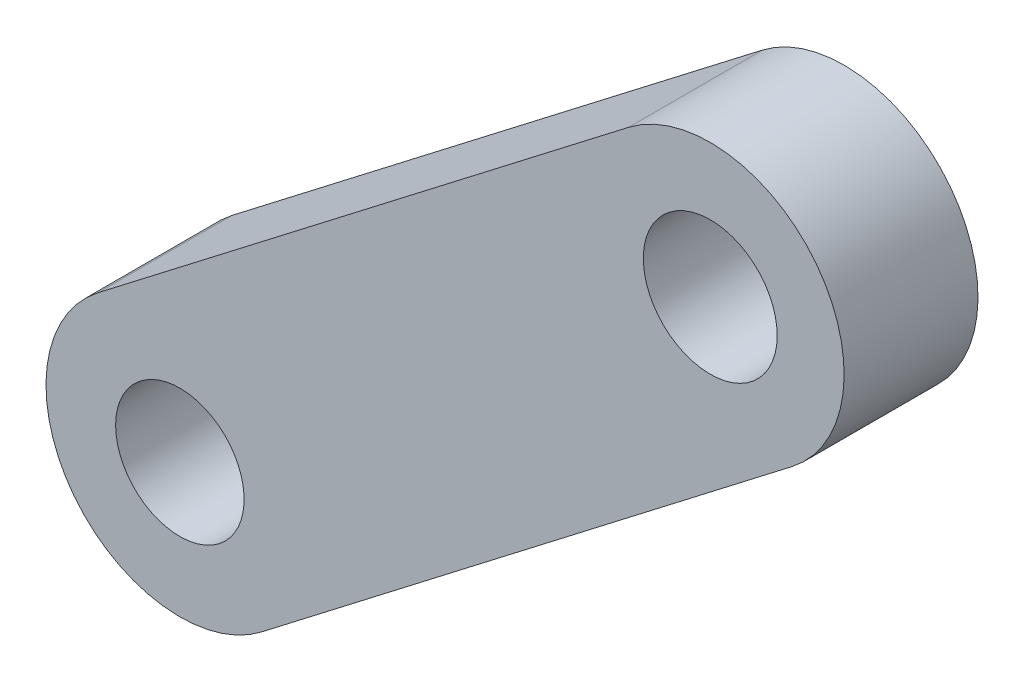
SolidWorks part; units mm, degrees
ref_plane "Front Plane" through (0, 0, 0) normal (0, 0, 1) x (1, 0, 0)
ref_plane "Top Plane" through (0, 0, 0) normal (0, 1, 0) x (1, 0, 0)
ref_plane "Right Plane" through (0, 0, 0) normal (1, 0, 0) x (0, 0, -1)
sketch "Sketch1" plane through (0, 0, 0) normal (0, 0, 1) x (0.9998, -0.022, 0)
  line L0 (-41.8829, 111.4723) -> (-17.0715, 91.626) construction
  line L1 (-1.7639, 79.3817) -> (-1.7639, 99.3817) construction
  line L2 (-1.7639, 99.3817) -> (-51.7712, 99.3817) construction
  line L3 (-46.2352, 83.6971) -> (-26.7675, 99.3817) construction
  line L4 (-46.2352, 83.6971) -> (-49.3722, 87.5906) construction
  line L5 (-49.3722, 87.5906) -> (-43.0983, 79.8035) construction
  line L6 (-49.3722, 87.5906) -> (-29.9044, 103.2753)
  line L7 (-43.0983, 79.8035) -> (-23.6306, 95.4882)
  line L8 (-29.9044, 103.2753) -> (-23.6306, 95.4882) construction
  circle A0 centre (-1.7639, 79.3817) radius 2.5 construction
  circle A1 centre (-1.7639, 79.3817) radius 2.5 construction
  circle A3 centre (-26.7675, 99.3817) radius 2.5
  arc A4 (-22.8629, 96.2585) -> (-30.6611, 96.2448) centre (-26.7675, 99.3817) ccw
  circle A6 centre (-46.2352, 83.6971) radius 1.5 construction
  arc A7 (-49.3722, 87.5906) -> (-43.0983, 79.8035) centre (-46.2352, 83.6971) ccw
  arc A8 (-23.6306, 95.4882) -> (-29.9044, 103.2753) centre (-26.7675, 99.3817) ccw
  point P18 (-26.7675, 99.3817)
  dimension "D1" = 5
  dimension "D2" = 5
  dimension "D4" = 5
  dimension "D5" = 3
  dimension "D6" = 10
  dimension "D3" = 20
  dimension "D7" = 25
extrude "Boss-Extrude1" add sketch "Sketch1" along normal blind 5 contours L7 A8 L6 A7 A3 A6 region at (-35.1054, 91.8366, 0)
sketch "Sketch2" plane through (0, 0, 0) normal (0, 0, -1) x (-1, 0, 0)
  circle A0 centre (44.3801, 84.6953) radius 2.4
  dimension "D1" = 4.8
extrude "Cut-Extrude1" cut sketch "Sketch2" against normal blind 5
sketch "Sketch4" plane through (0, 0, 0) normal (0, 0, -1) x (-1, 0, 0)
  line L0 (44.3801, 84.6953) -> (41.2108, 87.1357) construction
  line L1 (42.4785, 86.1595) -> (39.1522, 88.7207) construction
  line L2 (38.2371, 87.5322) -> (40.0673, 89.9092)
  line L3 (41.2108, 87.1357) -> (40.0673, 89.9092)
  line L4 (38.2371, 87.5322) -> (41.2108, 87.1357)
  line L5 (47.4305, 88.6571) -> (27.622, 103.909) construction
  circle A0 centre (44.3801, 84.6953) radius 2.4 construction
  point P7 (0, 0)
  point P10 (39.1522, 88.7207)
  point P11 (0, 0)
  dimension "D1" = 3
  dimension "D2" = 3
  dimension "D3" = 4
  dimension "D4" = 3
extrude "Cut-Extrude2" cut sketch "Sketch4" against normal blind 1
